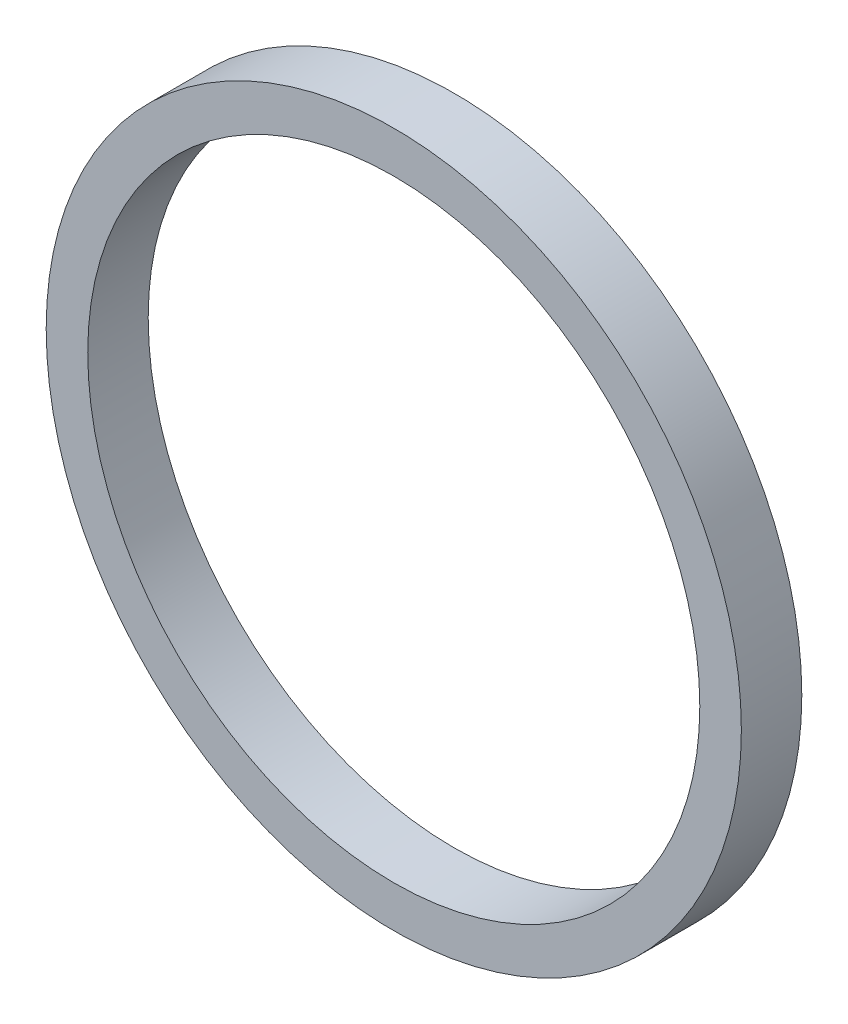
SolidWorks part; units mm, degrees
ref_plane "Front Plane" through (0, 0, 0) normal (0, 0, 1) x (1, 0, 0)
ref_plane "Top Plane" through (0, 0, 0) normal (0, 1, 0) x (1, 0, 0)
ref_plane "Right Plane" through (0, 0, 0) normal (1, 0, 0) x (0, 0, -1)
sketch "Sketch1" plane through (0, 0, 0) normal (0, 0, 1) x (1, 0, 0)
  circle A0 centre (0, 0) radius 5.0625
  circle A1 centre (0, 0) radius 5.75
  dimension "D1" = 10.125
  dimension "D2" = 11.5
extrude "Boss-Extrude1" add sketch "Sketch1" along normal blind 1
equation "\"RingPinShaft\"= 5"
equation "\"CenterBearingOut\"=32.125"
equation "\"RingPostIn\"=5.125"
equation "\"CamBearingOut\"=15.125"
equation "\"DiskOutputShaft\"=10"
equation "\"CenterShaft\"=25"
equation "\"Eccentricity\"=2"
equation "\"CycCamShaft\"=10"
equation "\"D1@Sketch1\"=\"CycCamShaft\" + 0.125"
equation "\"D2@Sketch1\"=\"CycCamShaft\"+1.5"
